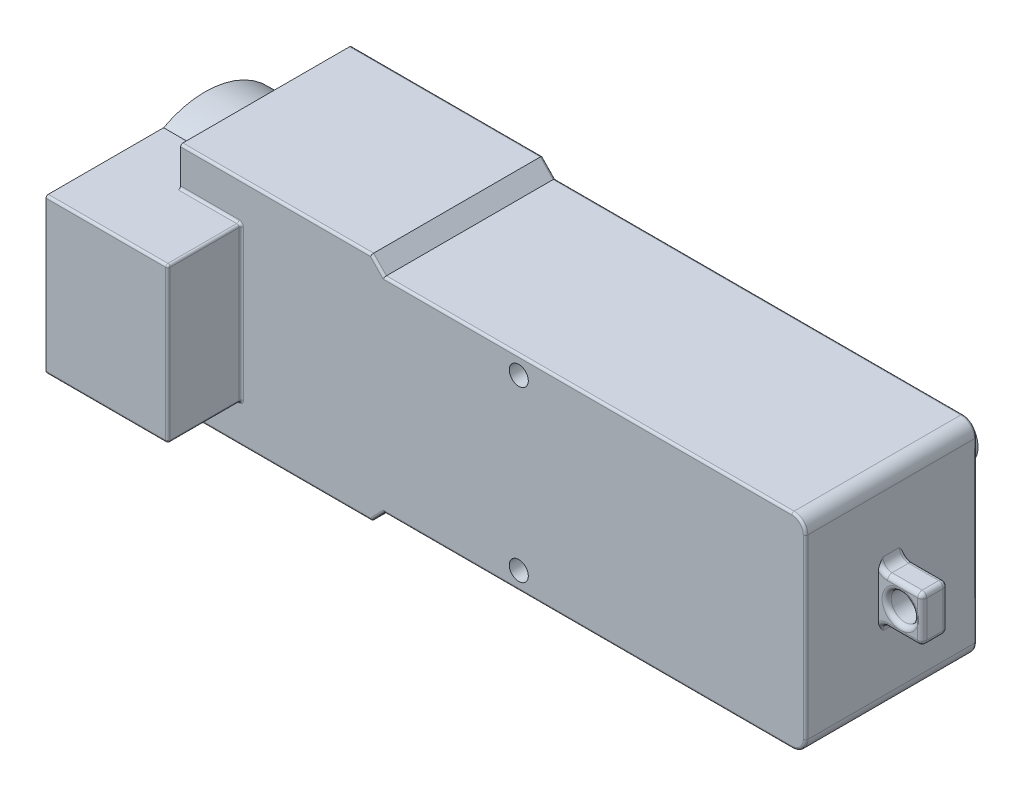
SolidWorks part; units mm, degrees
ref_plane "Front Plane" through (0, 0, 0) normal (0, 0, 1) x (1, 0, 0)
ref_plane "Top Plane" through (0, 0, 0) normal (0, 1, 0) x (1, 0, 0)
ref_plane "Right Plane" through (0, 0, 0) normal (1, 0, 0) x (0, 0, -1)
sketch "Sketch1" plane through (0, 0, 0) normal (0, 0, 1) x (1, 0, 0)
  line L0 (-342.25, 126.5) -> (-342.25, 96)
  line L1 (-342.25, 126.5) -> (-133.25, 126.5)
  line L2 (-409.25, 96) -> (-409.25, -96)
  line L3 (-342.25, -126.5) -> (-133.25, -126.5)
  line L4 (342.25, 97) -> (342.25, -97)
  line L5 (0, -126.5) -> (0, 126.5) construction
  line L6 (-409.25, 0) -> (342.25, 0) construction
  line L7 (-342.25, 96) -> (-409.25, 96)
  line L8 (-342.25, -126.5) -> (-342.25, -96)
  line L9 (-342.25, -96) -> (-409.25, -96)
  line L10 (327.25, 112) -> (-119.25, 112)
  line L11 (-119.25, 112) -> (-133.25, 126.5)
  line L12 (-119.25, -112) -> (-133.25, -126.5)
  line L13 (327.25, -112) -> (-119.25, -112)
  arc A0 (327.25, -112) -> (342.25, -97) centre (327.25, -97) ccw
  arc A1 (327.25, 112) -> (342.25, 97) centre (327.25, 97) cw
  point P10 (-375.75, 96)
  point P17 (342.25, -112)
  point P20 (342.25, 112)
  point P52 (0, 0)
  dimension "D8" = 15
  dimension "D1" = 224
  dimension "D2" = 253
  dimension "D3" = 192
  dimension "D4" = 67
  dimension "D5" = 223
  dimension "D6" = 751.5
  dimension "D7" = 209
extrude "Boss-Extrude1" add sketch "Sketch1" along normal blind 187.5
sketch "Sketch3" plane through (-409.25, 0, 0) normal (-1, 0, 0) x (0, 0, 1)
  line L2 (0, 96) -> (0, -96)
  line L4 (10, 46.7199) -> (10, -46.7199)
  line L6 (0, 0) -> (10, 0) construction
  line L7 (93.75, 96) -> (93.75, 0) construction
  line L8 (187.5, 96) -> (0, 96) construction
  line L9 (93.75, 0) -> (10, 0) construction
  line L10 (187.5, 84.5) -> (187.5, 96)
  line L11 (139.0993, 84.5) -> (267.9, 84.5)
  line L13 (139.0993, -84.5) -> (267.9, -84.5)
  line L14 (0, 96) -> (0, -96)
  line L15 (0, -96) -> (187.5, -96)
  line L16 (187.5, -96) -> (187.5, 96)
  line L17 (187.5, 96) -> (0, 96)
  line L18 (0, 96) -> (0, -96)
  line L19 (0, -96) -> (187.5, -96)
  line L20 (187.5, -96) -> (187.5, -84.5)
  line L21 (187.5, 96) -> (0, 96)
  line L22 (267.9, 84.5) -> (267.9, -84.5)
  line L23 (203.4997, -84.5) -> (203.4997, 84.5) construction
  line L24 (139.3104, 0) -> (267.9, 0) construction
  arc A1 (10, -46.7199) -> (139.0993, -84.5) centre (93.75, 0) ccw
  arc A2 (139.0993, 84.5) -> (10, 46.7199) centre (93.75, 0) ccw
  point P144 (203.4997, 0)
  point P304 (0.5, 0)
  line M5 (0, 96) -> (0, -96)
  line M6 (0, -96) -> (187.5, -96)
  line M7 (187.5, -96) -> (187.5, 96)
  line M8 (187.5, 96) -> (0, 96)
  dimension "D7" = 95.9
  dimension "D1" = 10
  dimension "D4" = 257.9
  dimension "D5" = 169
  dimension "D2" = 0
extrude "Cut-Extrude5" cut sketch "Sketch3" against normal up to surface (67 mm away) contours A2 L11 L13 A1 L4 M7 M8 M5 M6 region at (-409.25, 90.25, 184.8163) up to face at (-342.25, 111.25, 93.75)
sketch "Sketch4" plane through (-409.25, 0, 0) normal (-1, 0, 0) x (0, 0, 1)
  line L1 (267.9, 84.5) -> (187.5, 84.5)
  line L2 (267.9, 84.5) -> (267.9, -84.5)
  line L3 (267.9, -84.5) -> (187.5, -84.5)
  line L4 (187.5, 84.5) -> (187.5, -84.5)
  line L5 (227.7, -84.5) -> (227.7, 84.5) construction
  line L6 (267.9, 0) -> (187.5, 0) construction
  point P324 (227.7, 0)
extrude "Boss-Extrude2" add sketch "Sketch4" against normal blind 133.5
ref_plane "Plane1" through (0, 0, 93.75) normal (0, 0, -1) x (-1, 0, 0)
sketch "Sketch5" plane through (0, 0, 0) normal (0, 0, -1) x (-1, 0, 0)
  line L0 (0, 0) -> (-480.16, 0) construction
  line L1 (-342.25, -97) -> (-342.25, 97) construction
  line L2 (-342.25, 25) -> (-390.25, 25)
  line L3 (-342.25, 25) -> (-342.25, -25)
  line L4 (-342.25, -25) -> (-390.25, -25)
  line L5 (-390.25, 25) -> (-390.25, -25)
  line L6 (-366.25, -25) -> (-366.25, 25) construction
  line L7 (-342.25, 0) -> (-390.25, 0) construction
  line L8 (409.25, 84.5) -> (409.25, -84.5) construction
  circle A0 centre (-366.25, 0) radius 14.95
  point P223 (-366.25, 0)
  dimension "D3" = 29.9
  dimension "D1" = 799.5
  dimension "D2" = 50
extrude "Boss-Extrude3" add sketch "Sketch5" along normal blind 14 and the other way blind 14 from surface starting at plane "Plane1"
scale "Scale1" bodies to scale 105 scale about centroid uniform scaling yes scale factor 0.1
sketch "Sketch6" plane through (0, 0, 91.2651) normal (0, 0, -1) x (-1, 0, 0)
  line L0 (78.0616, 4.672) -> (78.0616, -4.672) construction
  line L1 (7.2116, 0) -> (78.0616, 0) construction
  circle A0 centre (32.0216, 0) radius 1.99 construction
  circle A1 centre (21.0216, 0) radius 2.7 construction
  circle A2 centre (41.0216, 9.2567) radius 1.0433
  circle A3 centre (41.0216, -9.2567) radius 1.0433
  point P0 (7.2116, 0)
  point P1 (78.0616, 0)
  point P13 (41.0216, 10.3)
  point P14 (41.0216, -10.3)
  dimension "D1" = 3.98
  dimension "D3" = 5.4
  dimension "D5" = 9
  dimension "D2" = 24.81
  dimension "D4" = 11
  dimension "D6" = 20.6
extrude "Cut-Extrude6" cut sketch "Sketch6" against normal up to next
sketch "Sketch7" plane through (0, 0, 91.2651) normal (0, 0, -1) x (-1, 0, 0)
  line L0 (7.2116, 0) -> (78.0616, 0) construction
  line L1 (19.0551, 1.85) -> (22.9882, 1.85)
  line L3 (19.0551, -1.85) -> (22.9882, -1.85)
  line L5 (21.0216, -1.85) -> (21.0216, 1.85) construction
  line L6 (19.0551, 0) -> (22.9882, 0) construction
  line L7 (21.0216, 2.7) -> (21.0216, -2.7) construction
  arc A0 (22.9882, -1.85) -> (22.9882, 1.85) centre (21.0216, 0) ccw
  circle A1 centre (21.0216, 0) radius 2.7 construction
  arc A2 (19.0551, 1.85) -> (19.0551, -1.85) centre (21.0216, 0) ccw
  point P0 (21.0216, 2.7)
  point P7 (21.0216, -2.7)
  point P186 (21.0216, 0)
  dimension "D2" = 2.7
  dimension "D1" = 3.7
extrude "Boss-Extrude4" add sketch "Sketch7" along normal blind 8.85
sketch "Sketch8" plane through (0, 0, 91.2651) normal (0, 0, -1) x (-1, 0, 0)
  circle A0 centre (32.0216, 0) radius 1.99 construction
  circle A1 centre (32.0216, 0) radius 1.99
extrude "Boss-Extrude5" add sketch "Sketch8" along normal blind 1.77
fillet "Fillet1" radius 1 2 edges at (-9.6116, 2.5, 100.6401) (-9.6116, -2.5, 100.6401)
fillet "Fillet2" radius 0.5 14 edges at (-9.3188, -2.7929, 102.0401) (-9.3188, -2.7929, 99.2401) (-9.3188, 2.7929, 102.0401) (-9.3188, 2.7929, 99.2401) (-8.7066, 0, 99.2401) (-8.7066, 0, 102.0401) (-6.7116, -2.5, 102.0401) (-6.7116, -2.5, 99.2401) (-4.8116, 0, 102.0401) (-4.8116, -2.5, 100.6401) (-4.8116, 0, 99.2401) (-6.7116, 2.5, 102.0401) (-6.7116, 2.5, 99.2401) (-4.8116, 2.5, 100.6401)
fillet "Fillet3" radius 0.25 29 edges at (-78.0616, -8.45, 107.5951) (-74.7366, 8.45, 110.0151) (-74.7366, -8.45, 110.0151) (-33.4366, -11.2, 110.0151) (-10.051, -10.7607, 110.0151) (-9.6116, 0, 110.0151) (-10.051, 10.7607, 110.0151) (-33.4366, 11.2, 91.2651) (-10.051, 10.7607, 91.2651) (-9.6116, 0, 91.2651) (-10.051, -10.7607, 91.2651) (-71.4116, 0, 110.0151) (-71.4116, 8.45, 114.0351) (-71.4116, -8.45, 114.0351) (-78.0866, 8.45, 118.0551) (-78.0866, -8.45, 118.0551) (-71.4116, 0, 118.0551) (-78.0616, -10.55, 110.0151) (-67.6116, -12.65, 110.0151) (-56.4616, -11.925, 110.0151) (-33.4366, 11.2, 110.0151) (-56.4616, 11.925, 110.0151) (-67.6116, 12.65, 110.0151) (-67.6116, 12.65, 91.2651) (-56.4616, 11.925, 91.2651) (-78.0616, 0, 91.2651) (-67.6116, -12.65, 91.2651) (-56.4616, -11.925, 91.2651) (-33.4366, -11.2, 91.2651)
